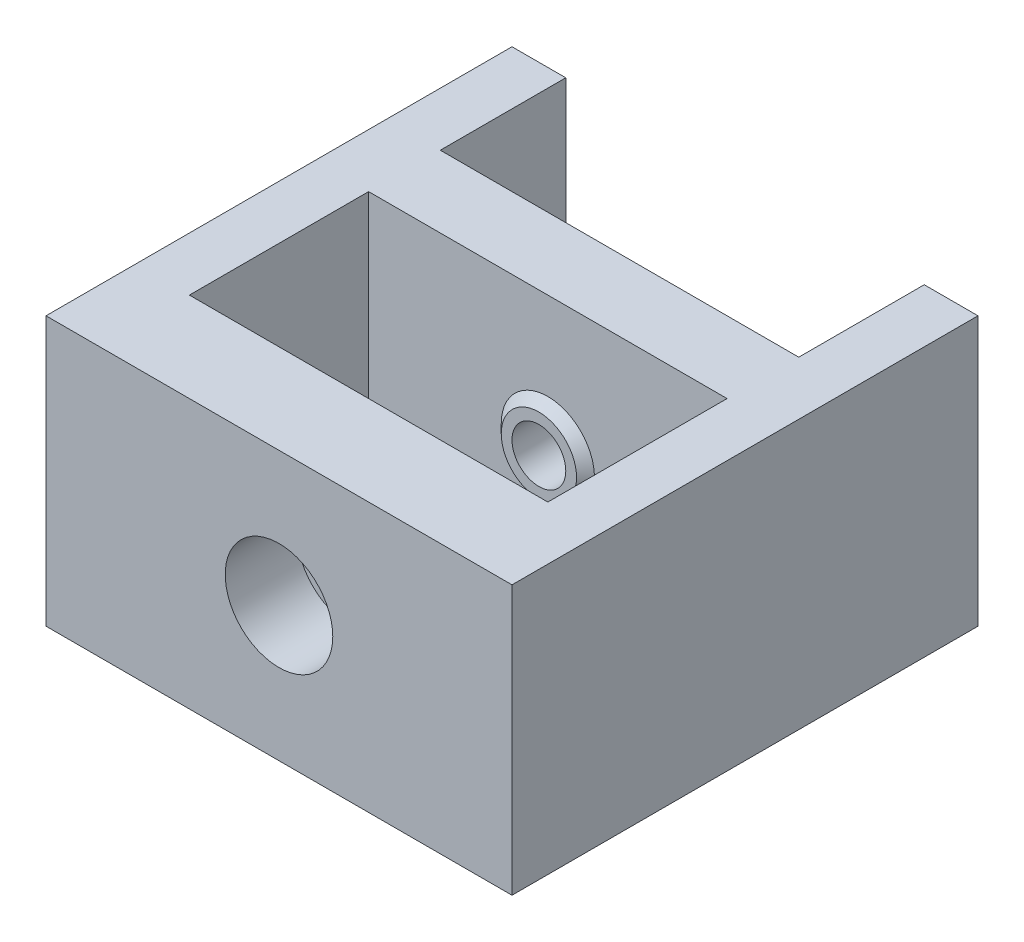
SolidWorks part; units mm, degrees
ref_plane "Front Plane" through (0, 0, 0) normal (0, 0, 1) x (1, 0, 0)
ref_plane "Top Plane" through (0, 0, 0) normal (0, 1, 0) x (1, 0, 0)
ref_plane "Right Plane" through (0, 0, 0) normal (1, 0, 0) x (0, 0, -1)
sketch "Sketch1" plane through (0, 0, 0) normal (0, 1, 0) x (1, 0, 0)
  line L1 (-13, -13) -> (13, -13)
  line L2 (-13, -13) -> (-13, 13)
  line L3 (-13, 13) -> (13, 13)
  line L4 (13, -13) -> (13, 13)
  line L5 (-13, -13) -> (13, 13) construction
  line L6 (-13, 13) -> (13, -13) construction
  point P0 (0, 0)
  dimension "D1" = 26
  dimension "D2" = 26
extrude "Boss-Extrude1" add sketch "Sketch1" along normal blind 15
sketch "Sketch3" plane through (0, 15, 0) normal (0, 1, 0) x (1, 0, 0)
  line L0 (-13, 13) -> (-13, -13) construction
  line L1 (-10, -8) -> (10, -8)
  line L2 (-10, -8) -> (-10, 2)
  line L3 (-10, 2) -> (10, 2)
  line L4 (10, -8) -> (10, 2)
  line L5 (13, -13) -> (13, 13) construction
  line L6 (-13, -13) -> (13, -13) construction
  dimension "D1" = 3
  dimension "D2" = 3
  dimension "D3" = 5
  dimension "D4" = 10
extrude "Cut-Extrude1" cut sketch "Sketch3" against normal blind 20
sketch "Sketch4" plane through (0, 15, 0) normal (0, -1, 0) x (1, 0, 0)
  line L0 (13, -13) -> (-13, -13) construction
  line L1 (-10, -13) -> (10, -13)
  line L2 (-10, -13) -> (-10, -6)
  line L3 (-10, -6) -> (10, -6)
  line L4 (10, -13) -> (10, -6)
  line L7 (10, -2) -> (-10, -2) construction
  line L9 (-10, -2) -> (-10, 8) construction
  line L10 (10, 8) -> (10, -2) construction
  dimension "D1" = 4
extrude "Cut-Extrude2" cut sketch "Sketch4" along normal offset from surface (10.5 mm away) 4.5 up to face at (0, 0, 3)
sketch "Sketch5" plane through (0, 4.5, 0) normal (0, 1, 0) x (1, 0, 0)
  line L0 (-10, 9.5) -> (10, 9.5) construction
  line L1 (-10, 6) -> (-10, 13) construction
  line L2 (10, 13) -> (10, 6) construction
  line L3 (0, 13) -> (0, 6) construction
  line L4 (-10, 13) -> (10, 13) construction
  line L5 (10, 6) -> (-10, 6) construction
  circle A0 centre (0, 9.5) radius 2.1
  dimension "D1" = 4.2
extrude "Cut-Extrude3" cut sketch "Sketch5" against normal through all
sketch "Sketch8" plane through (0, 0, -6) normal (0, 0, -1) x (-1, 0, 0)
  line L0 (-10, 7.5) -> (10, 7.5) construction
  line L3 (-10, 15) -> (10, 15) construction
  line L6 (10, 4.5) -> (10, 15) construction
  line L7 (-10, 4.5) -> (-10, 15) construction
  circle A0 centre (0, 7.5) radius 1.5
  point P10 (0, 0)
  point P11 (10, 7.5)
  point P14 (-10, 7.5)
  dimension "D1" = 3
  dimension "D2" = 7.5
extrude "Cut-Extrude6" cut sketch "Sketch8" against normal through all
sketch "Sketch9" plane through (0, 0, 13) normal (0, 0, 1) x (1, 0, 0)
  circle A0 centre (0, 7.5) radius 3
  dimension "D1" = 6
extrude "Cut-Extrude7" cut sketch "Sketch9" against normal blind 4
chamfer "Chamfer3" distance 0.5 angle 45 1 edges at (0, 4.5, -7.4)
sketch "Sketch10" plane through (0, 4.5, 0) normal (0, 1, 0) x (1, 0, 0)
  line L0 (10, 6) -> (-10, 6) construction
  line L1 (-10, 13) -> (-4, 13)
  line L2 (-10, 13) -> (-10, 6)
  line L3 (-10, 6) -> (-4, 6)
  line L4 (-4, 13) -> (-4, 6)
  line L5 (10, 6) -> (-10, 6) construction
  line L6 (10, 13) -> (4, 13)
  line L7 (10, 13) -> (10, 6)
  line L8 (10, 6) -> (4, 6)
  line L9 (4, 13) -> (4, 6)
  dimension "D1" = 6
  dimension "D2" = 6
extrude "Cut-Extrude8" cut sketch "Sketch10" against normal through all
chamfer "Chamfer4" distance 0.8 angle 45 1 edges at (0, 4.5, -6)
sketch "Sketch11" plane through (0, 0, -2) normal (0, 0, 1) x (1, 0, 0)
  circle A0 centre (0, 7.5) radius 2.1
  circle A1 centre (0, 7.5) radius 1.5
  dimension "D1" = 0.6
extrude "Boss-Extrude2" add sketch "Sketch11" along normal blind 0.5
sketch "Sketch12" plane through (0, 0, 8) normal (0, 0, -1) x (-1, 0, 0)
  circle A0 centre (0, 7.5) radius 2.1
  circle A1 centre (0, 7.5) radius 1.5
  dimension "D1" = 0.6
extrude "Boss-Extrude3" add sketch "Sketch12" along normal blind 0.5
chamfer "Chamfer5" distance 0.5 angle 45 2 edges at (-2.1, 7.5, -2) (2.1, 7.5, 8)
